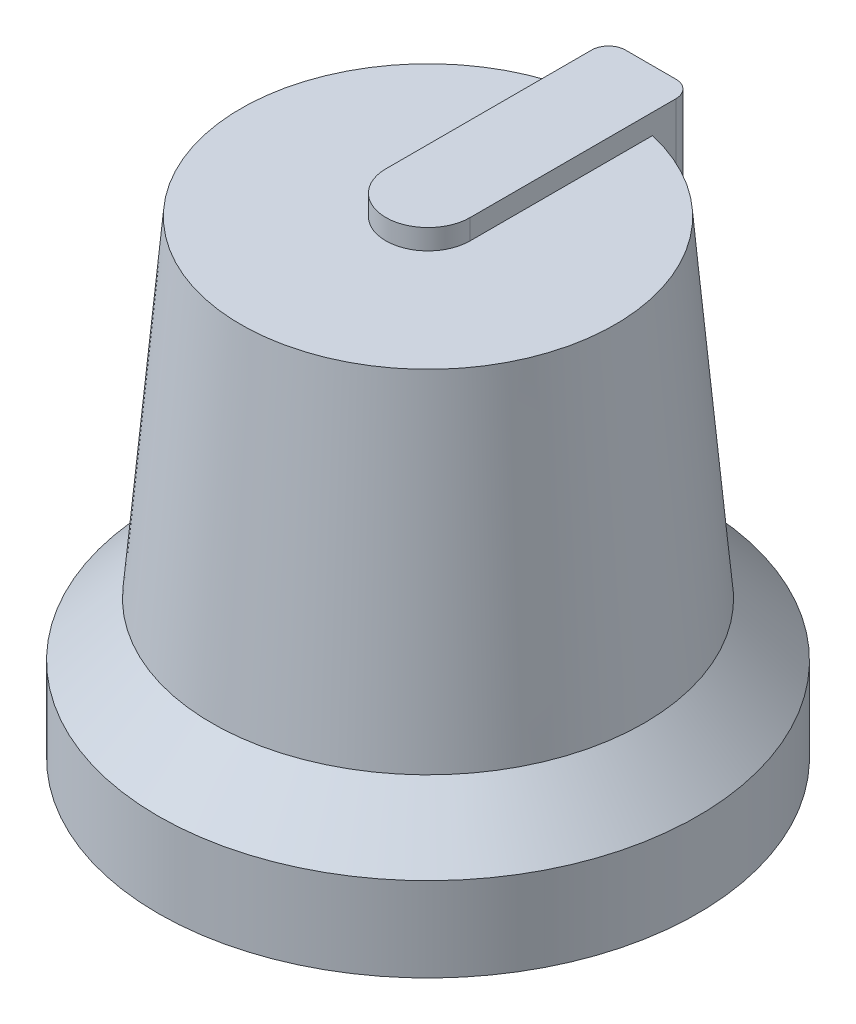
SolidWorks part; units mm, degrees
ref_plane "Front Plane" through (0, 0, 0) normal (0, 0, 1) x (1, 0, 0)
ref_plane "Top Plane" through (0, 0, 0) normal (0, 1, 0) x (1, 0, 0)
ref_plane "Right Plane" through (0, 0, 0) normal (1, 0, 0) x (0, 0, -1)
sketch "Sketch1" plane through (0, 0, 0) normal (0, 0, 1) x (1, 0, 0)
  line L0 (0, 0) -> (0, 18.7389) construction
  line L1 (0, 13.9) -> (5.55, 13.9)
  line L2 (5.55, 13.9) -> (6.4081, 4.0919)
  line L3 (6.4081, 4.0919) -> (8, 2.5)
  line L4 (8, 2.5) -> (8, 0)
  line L5 (8, 0) -> (0, 0)
  line L6 (0, 0) -> (0, 13.9)
  point P5 (5.55, 13.9)
  point P9 (5.9142, 4.5858)
  dimension "D1" = 13.9
  dimension "D2" = 16
  dimension "D3" = 11.1
  dimension "D4" = 2.5
  dimension "D5" = 45
  dimension "D6" = 140
revolve "Revolve1" add sketch "Sketch1" angle 360 about L0
sketch "Sketch2" plane through (0, 13.9, 0) normal (0, 1, 0) x (1, 0, 0)
  line L0 (-1.25, 6.104) -> (-1.25, 0)
  line L5 (-0.75, 6.604) -> (0.75, 6.604)
  line L7 (1.25, 0) -> (1.25, 6.104)
  arc A0 (-1.25, 0) -> (1.25, 0) centre (0, 0) ccw
  arc A1 (1.25, 6.104) -> (0.75, 6.604) centre (0.75, 6.104) ccw
  arc A2 (-1.25, 6.104) -> (-0.75, 6.604) centre (-0.75, 6.104) cw
  point P1 (0, 6.604)
  point P5 (-0.7532, 6.8044)
  point P7 (-1.064, 6.7762)
  dimension "D1" = 1.25
  dimension "D3" = 0.5
  dimension "D2" = 6.604
extrude "Boss-Extrude1" add sketch "Sketch2" against normal up to next and the other way blind 0.6
sketch "Sketch3" plane through (0, 0, 0) normal (0, 1, 0) x (1, 0, 0)
  circle A0 centre (0, 0) radius 3
  dimension "D1" = 6
extrude "Cut-Extrude1" cut sketch "Sketch3" along normal blind 12
